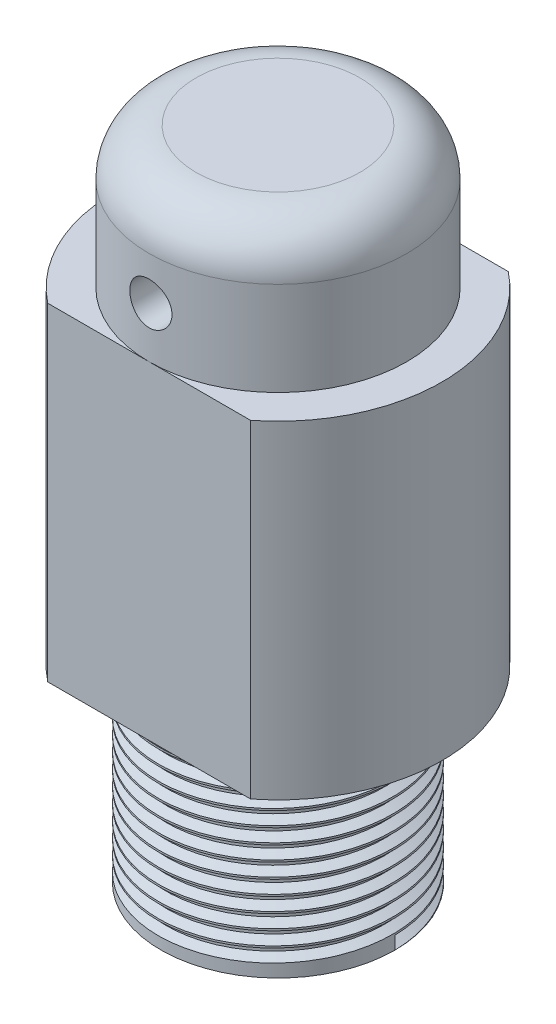
SolidWorks part; units mm, degrees
material "Stainless Steel (ferritic)"
ref_plane "Front Plane" through (0, 0, 0) normal (0, 0, 1) x (1, 0, 0)
ref_plane "Top Plane" through (0, 0, 0) normal (0, 1, 0) x (1, 0, 0)
ref_plane "Right Plane" through (0, 0, 0) normal (1, 0, 0) x (0, 0, -1)
sketch "Sketch1" plane through (0, 0, 0) normal (0, 1, 0) x (1, 0, 0)
  line L0 (-2.1651, 2.75) -> (2.1651, 2.75)
  line L1 (-2.1651, -2.75) -> (2.1651, -2.75)
  arc A0 (-2.1651, 2.75) -> (-2.1651, -2.75) centre (0, 0) ccw
  arc A1 (2.1651, -2.75) -> (2.1651, 2.75) centre (0, 0) ccw
  dimension "D1" = 7
  dimension "D2" = 2.75
  dimension "D3" = 2.75
extrude "Boss-Extrude2" add sketch "Sketch1" along normal blind 7 contours A0 L1 A1 L0
sketch "Sketch2" plane through (0, 7, 0) normal (0, 1, 0) x (1, 0, 0)
  circle A0 centre (0, 0) radius 2.75
extrude "Boss-Extrude4" add sketch "Sketch2" along normal blind 3 contours A0
sketch "Sketch3" plane through (0, 0, 0) normal (0, -1, 0) x (1, 0, 0)
  circle A0 centre (0, 0) radius 2.5
  dimension "D1" = 5
extrude "Boss-Extrude5" add sketch "Sketch3" along normal blind 4
thread "Thread1" pitch 0.3175 method cut profile "Thread Profile1" start angle 0, offset 0, length 0, pitch 0.3175, diameter 5
ref_plane "Plane1" through (2.5, -4, 0) normal (0, 0, 1) x (1, 0, 0)
sketch "Thread Profile1" plane through (2.5, -4, 0) normal (0, 0, 1) x (1, 0, 0)
  line L0 (0, 0) -> (0, 0.3175) construction
  line L11 (0, 0) -> (0, 0.2778)
  line L12 (0, 0.2778) -> (-0.1719, 0.1786)
  line L13 (-0.1719, 0.1786) -> (-0.1719, 0.0992)
  line L15 (-0.1719, 0.0992) -> (0, 0)
  line L17 (-0.1719, 0.1389) -> (0, 0.1389) construction
  point P2 (0, 0)
  dimension "Pitch" = 0.3175
  dimension "Profile_Angle" = 60
  dimension "Profile_Land" = 0.0794
  dimension "Profile_Height" = 0.1719
sketch "Sketch10" plane through (0, -4, 0) normal (0, -1, 0) x (1, 0, 0)
  circle A0 centre (0, 0) radius 0.5
  dimension "D1" = 1
extrude "Cut-Extrude1" cut sketch "Sketch10" against normal blind 13
fillet "Fillet1" radius 1 1 edges at (0, 10, 2.75)
sketch "Sketch11" plane through (0, 0, 2.75) normal (0, 0, 1) x (1, 0, 0)
  circle A0 centre (0, 8.0778) radius 0.45
  dimension "D1" = 0.9
extrude "Cut-Extrude2" cut sketch "Sketch11" against normal blind 3
ref_axis "Axis1" through (0, 9, 0) along (0, -1, 0)
